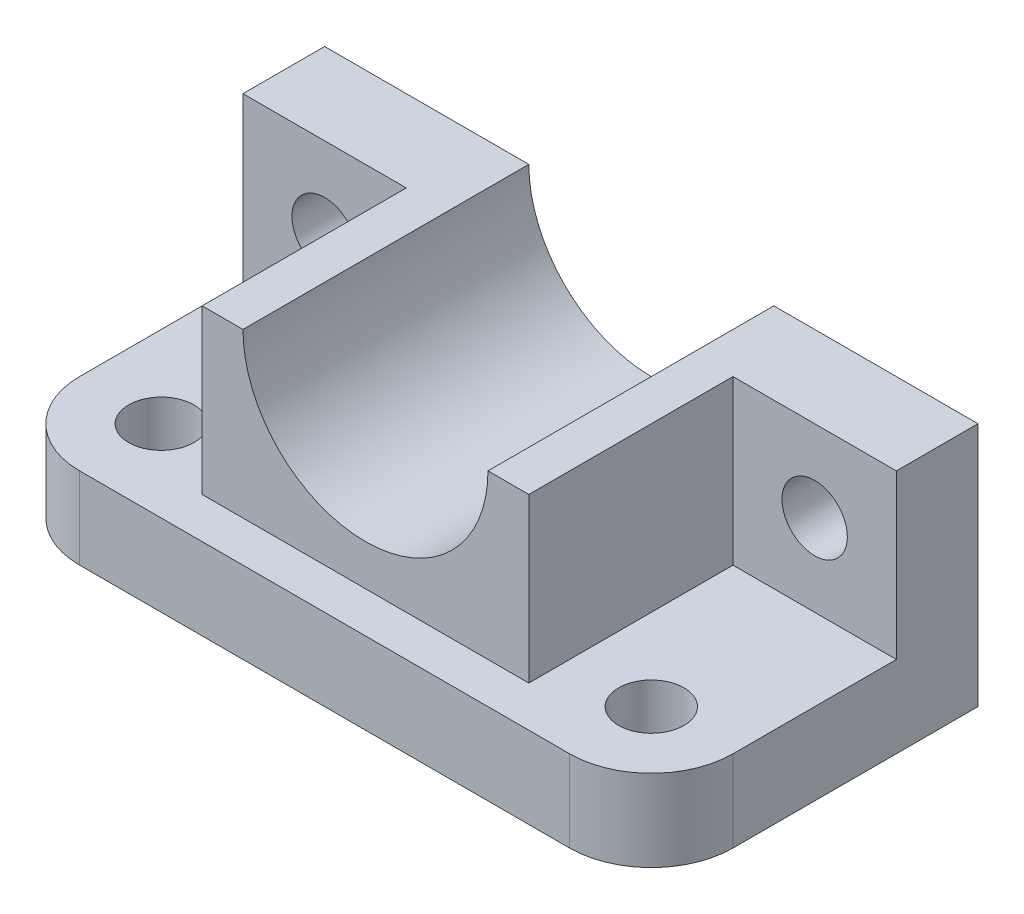
SolidWorks part; units mm, degrees
ref_plane "Front Plane" through (0, 0, 0) normal (0, 0, 1) x (1, 0, 0)
ref_plane "Top Plane" through (0, 0, 0) normal (0, 1, 0) x (1, 0, 0)
ref_plane "Right Plane" through (0, 0, 0) normal (1, 0, 0) x (0, 0, -1)
sketch "Sketch1" plane through (0, 0, 0) normal (0, 1, 0) x (1, 0, 0)
  line L1 (-30, -20) -> (30, -20)
  line L2 (-40, -10) -> (-40, 20)
  line L3 (-40, 20) -> (40, 20)
  line L4 (40, -10) -> (40, 20)
  line L5 (-40, -20) -> (40, 20) construction
  line L6 (-40, 20) -> (40, -20) construction
  arc A0 (40, -10) -> (30, -20) centre (30, -10) cw
  arc A1 (-30, -20) -> (-40, -10) centre (-30, -10) cw
  circle A2 centre (-30, -10) radius 4
  circle A3 centre (30, -10) radius 4
  point P0 (0, 0)
  dimension "D3" = 10
  dimension "D4" = 8
  dimension "D1" = 80
  dimension "D2" = 40
extrude "Boss-Extrude1" add sketch "Sketch1" along normal blind 10
sketch "Sketch2" plane through (0, 0, -20) normal (0, 0, -1) x (-1, 0, 0)
  line L0 (40, 0) -> (40, 30)
  line L1 (-40, 0) -> (40, 0) construction
  line L2 (-40, 0) -> (40, 0)
  line L3 (0, 5.5) -> (0, -5.5) construction
  line L4 (-40, 0) -> (-40, 30)
  line L5 (-40, 30) -> (-20, 30)
  line L6 (40, 30) -> (20, 30)
  line L7 (-20, 30) -> (20, 30) construction
  line L8 (-20, 30) -> (-20, 0)
  line L10 (-20, 30) -> (-15, 30)
  line L11 (20, 30) -> (20, 0)
  line L12 (20, 30) -> (15, 30)
  arc A0 (-15, 30) -> (15, 30) centre (0, 30) ccw
  point P2 (-20, 0)
  point P14 (20, 0)
  line M6 (-40, 0) -> (40, 0)
  line M7 (40, 0) -> (40, 10)
  line M8 (40, 10) -> (-40, 10)
  line M9 (-40, 10) -> (-40, 0)
  dimension "D3" = 30
  dimension "D1" = 30
  dimension "D2" = 20
extrude "Boss-Extrude2" add sketch "Sketch2" against normal blind 10 contours L8 L5 L4 M8 | L8 M8 M9 M6 | L6 L11 L0 M8 | L11 M8 M6 M7 | L11 L8 L2 M8 region at (-30, 5, -20) region at (-30, 20, -20) region at (0, 5, -20) region at (30, 5, -20) region at (30, 20, -20)
extrude "Boss-Extrude3" add sketch "Sketch2<3>" against normal blind 35 contours A0 L10 L8 L11 L12 M8 region at (0, 10.4472, -20)
sketch "Sketch2<3>" plane through (0, 0, -20) normal (0, 0, -1) x (-1, 0, 0) same geometry as "Sketch2"
sketch "Sketch3" plane through (0, 0, -10) normal (0, 0, 1) x (1, 0, 0)
  line L0 (20, 10) -> (40, 30) construction
  line L1 (0, -16.5) -> (0, 16.5) construction
  circle A0 centre (30, 20) radius 4
  circle A1 centre (-30, 20) radius 4
  point P6 (30, 20)
  dimension "D1" = 8
extrude "Cut-Extrude1" cut sketch "Sketch3" against normal through all
